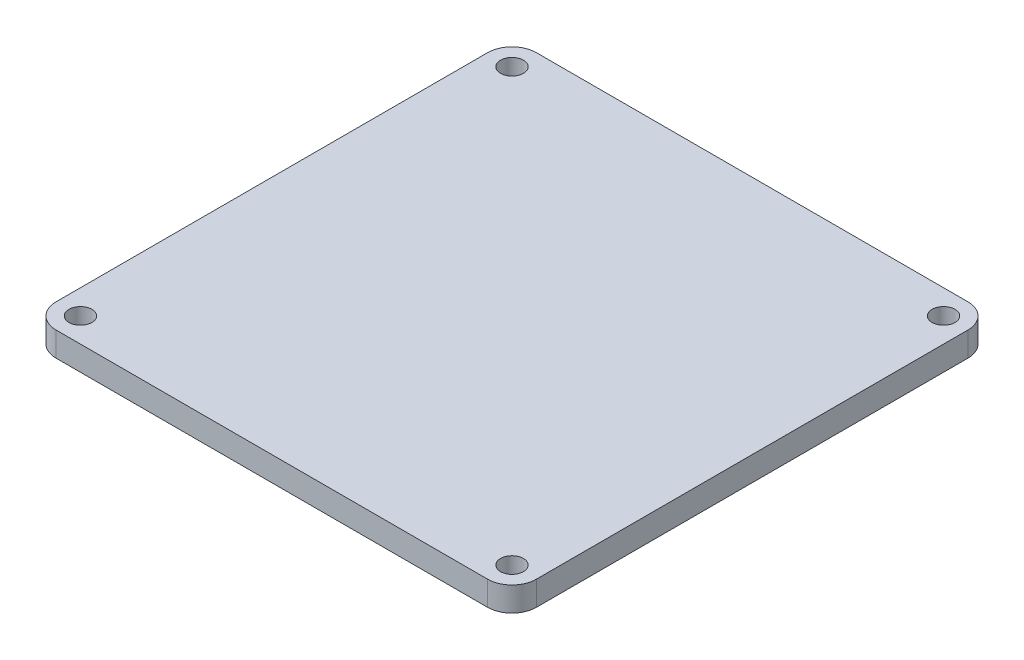
SolidWorks part; units mm, degrees
other "DetailItem2"
material "6061 Alloy"
ref_plane "Front Plane" through (0, 0, 0) normal (0, 0, 1) x (1, 0, 0)
ref_plane "Top Plane" through (0, 0, 0) normal (0, 1, 0) x (1, 0, 0)
ref_plane "Right Plane" through (0, 0, 0) normal (1, 0, 0) x (0, 0, -1)
sketch "Sketch1" plane through (0, 0, 0) normal (0, 1, 0) x (1, 0, 0)
  line L0 (-89.8026, 99.9626) -> (89.8026, 99.9626)
  line L1 (-89.8026, -89.8026) -> (89.8026, -89.8026) construction
  line L2 (-89.8026, -89.8026) -> (-89.8026, 89.8026) construction
  line L3 (-89.8026, 89.8026) -> (89.8026, 89.8026) construction
  line L4 (89.8026, -89.8026) -> (89.8026, 89.8026) construction
  line L5 (-89.8026, -89.8026) -> (89.8026, 89.8026) construction
  line L6 (-89.8026, 89.8026) -> (89.8026, -89.8026) construction
  line L7 (-99.9626, 89.8026) -> (-99.9626, -89.8026)
  line L8 (-89.8026, -99.9626) -> (89.8026, -99.9626)
  line L9 (99.9626, 89.8026) -> (99.9626, -89.8026)
  circle A0 centre (0, 0) radius 152.4 construction
  circle A1 centre (0, 0) radius 139.7 construction
  circle A2 centre (89.8026, 89.8026) radius 4.7625
  arc A7 (99.9626, 89.8026) -> (89.8026, 99.9626) centre (89.8026, 89.8026) ccw
  arc A8 (89.8026, -99.9626) -> (99.9626, -89.8026) centre (89.8026, -89.8026) ccw
  circle A9 centre (89.8026, -89.8026) radius 4.7625
  arc A10 (-99.9626, -89.8026) -> (-89.8026, -99.9626) centre (-89.8026, -89.8026) ccw
  circle A11 centre (-89.8026, -89.8026) radius 4.7625
  arc A12 (-89.8026, 99.9626) -> (-99.9626, 89.8026) centre (-89.8026, 89.8026) ccw
  circle A13 centre (-89.8026, 89.8026) radius 4.7625
  point P26 (0, 0)
  dimension "D2" = 279.4
  dimension "D3" = 304.8
  dimension "D4" = 9.525
  dimension "D5" = 10.16
  dimension "D1" = 254
  dimension "D6" = 90
  dimension "D7" = 4
extrude "Boss-Extrude2" add sketch "Sketch1" along normal blind 5.08 and the other way blind 5.08
equation "\"Rocket Diameter\"=12"
equation "\"D2@Sketch1\"=\"Rocket Diameter\"-1"
equation "\"D1@Sketch1\"=\"Rocket Diameter\"-2"
equation "\"D3@Sketch1\"=\"Rocket Diameter\""
equation "\"Avionics Threaded Rod Diameter\"= 0.375in"
equation "\"Avionics Plate Corner Radius\"= 0.4"
equation "\"D4@Sketch1\"=\"Avionics Threaded Rod Diameter\""
equation "\"D5@Sketch1\"=\"Avionics Plate Corner Radius\""
